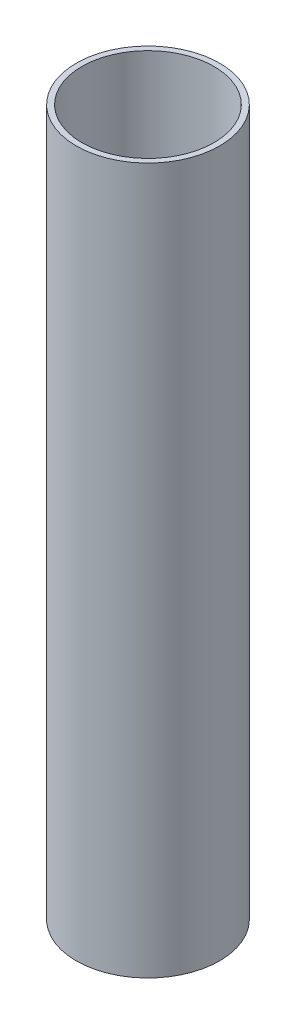
SolidWorks part; units mm, degrees
ref_plane "Front Plane" through (0, 0, 0) normal (0, 0, 1) x (1, 0, 0)
ref_plane "Top Plane" through (0, 0, 0) normal (0, 1, 0) x (1, 0, 0)
ref_plane "Right Plane" through (0, 0, 0) normal (1, 0, 0) x (0, 0, -1)
sketch "Sketch1" plane through (0, 0, 0) normal (0, 1, 0) x (1, 0, 0)
  circle A0 centre (0, 0) radius 25.4
  circle A1 centre (0, 0) radius 23.4
  dimension "Outer_Dia" = 50.8
  dimension "Inner_Dia" = 46.8
extrude "Boss-Extrude1" add sketch "Sketch1" along normal mid plane 250
